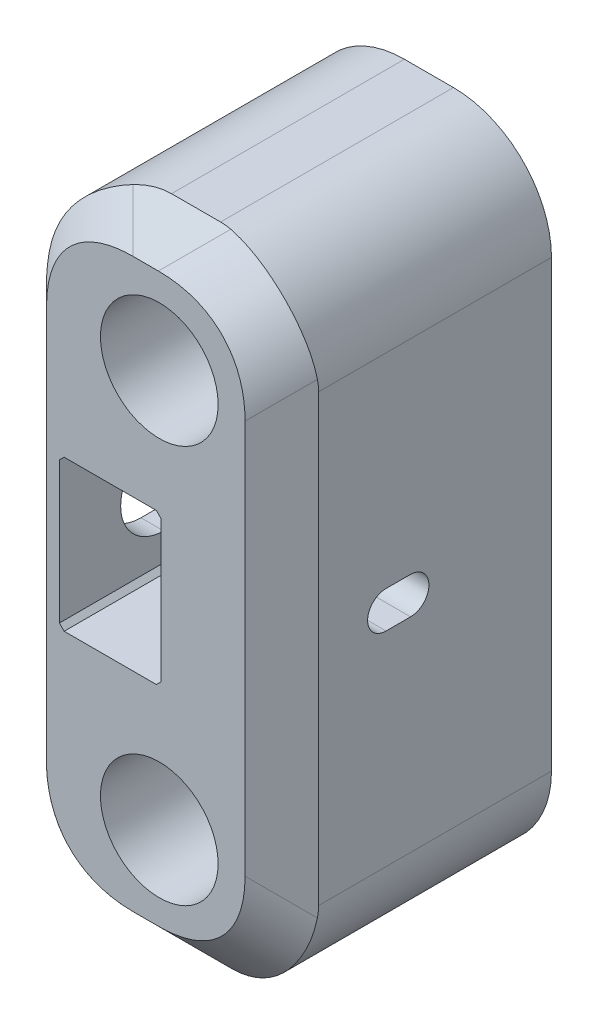
SolidWorks part; units mm, degrees
material "ABS"
ref_plane "Płaszczyzna przednia" through (0, 0, 0) normal (0, 0, 1) x (1, 0, 0)
ref_plane "Płaszczyzna górna" through (0, 0, 0) normal (0, 1, 0) x (1, 0, 0)
ref_plane "Płaszczyzna prawa" through (0, 0, 0) normal (1, 0, 0) x (0, 0, -1)
sketch "Szkic1" plane through (0, 0, 0) normal (0, 0, 1) x (1, 0, 0)
  line L0 (-32.7422, 138.1139) -> (-31.6012, 138.1139) construction
  line L1 (-31.3012, 137.8139) -> (-31.6012, 138.1139) construction
  line L2 (-31.3012, 137.8139) -> (-31.3012, 126.4139) construction
  line L3 (-31.6012, 126.1139) -> (-31.3012, 126.4139) construction
  line L4 (-31.6012, 126.1139) -> (-32.7422, 126.1139) construction
  line L5 (-33.0512, 126.6139) -> (-33.0512, 127.1139) construction
  line L6 (-33.0512, 127.1139) -> (-33.5512, 127.1139) construction
  line L7 (-33.5512, 127.1139) -> (-33.5512, 126.6139) construction
  line L8 (-39.3012, 126.4139) -> (-39.0012, 126.1139) construction
  line L9 (-33.8602, 126.1139) -> (-39.0012, 126.1139) construction
  line L10 (-39.3012, 126.4139) -> (-39.3012, 137.8139) construction
  line L11 (-39.0012, 138.1139) -> (-39.3012, 137.8139) construction
  line L12 (-33.5512, 137.6139) -> (-33.5512, 137.1139) construction
  line L13 (-33.5512, 137.1139) -> (-33.0512, 137.1139) construction
  line L14 (-33.0512, 137.1139) -> (-33.0512, 137.6139) construction
  line L15 (-39.0012, 138.1139) -> (-33.8602, 138.1139) construction
  line L16 (-21.3012, -182.8861) -> (-21.3012, 217.1139) construction
  line L17 (-41.3012, -182.8861) -> (-41.3012, 217.1139) construction
  line L18 (-28.2012, -182.8861) -> (-28.2012, 217.1139) construction
  line L19 (-34.4012, -182.8861) -> (-34.4012, 217.1139) construction
  line L20 (-33.8602, 138.1139) -> (-32.7422, 138.1139) construction
  line L21 (-33.8602, 126.1139) -> (-32.7422, 126.1139) construction
  line L22 (-33.8602, 125.9639) -> (-39.0633, 125.9639)
  line L23 (-39.4512, 126.3517) -> (-39.0633, 125.9639)
  line L24 (-39.4512, 126.3517) -> (-39.4512, 137.876)
  line L25 (-39.0633, 138.2639) -> (-39.4512, 137.876)
  line L26 (-39.0633, 138.2639) -> (-33.8602, 138.2639)
  line L27 (-33.5602, 126.1139) -> (-33.5602, 125.9639) construction
  line L28 (-32.7422, 138.2639) -> (-31.5391, 138.2639)
  line L29 (-31.1512, 137.876) -> (-31.5391, 138.2639)
  line L30 (-31.1512, 137.876) -> (-31.1512, 126.3517)
  line L31 (-31.5391, 125.9639) -> (-31.1512, 126.3517)
  line L32 (-31.5391, 125.9639) -> (-32.7422, 125.9639)
  line L33 (-33.5602, 125.9639) -> (-33.8602, 125.9639)
  line L36 (-33.417, 126.3455) -> (-33.1854, 126.3455) construction
  line L37 (-33.0422, 126.1139) -> (-33.0422, 125.9639) construction
  line L38 (-33.0422, 125.9639) -> (-32.7422, 125.9639)
  line L39 (-33.8602, 138.2639) -> (-33.5602, 138.2639)
  line L40 (-33.5602, 138.2639) -> (-33.5602, 138.1139) construction
  line L41 (-32.7422, 138.2639) -> (-33.0422, 138.2639)
  line L42 (-33.0422, 138.2639) -> (-33.0422, 138.1139) construction
  line L43 (-33.417, 137.8822) -> (-33.1854, 137.8822) construction
  line L44 (-41.3012, 132.1139) -> (-21.3012, 132.1139) construction
  line L45 (-41.3012, 105.9639) -> (-41.3012, 158.2639)
  line L46 (-41.3012, 158.2639) -> (-21.3012, 158.2639)
  line L47 (-21.3012, 158.2639) -> (-21.3012, 105.9639)
  line L48 (-41.3012, 105.9639) -> (-21.3012, 105.9639)
  line L49 (-31.3012, 158.2639) -> (-31.3012, 138.2639) construction
  line L50 (-33.5602, 138.2639) -> (-33.0422, 138.2639)
  line L51 (-33.5602, 125.9639) -> (-33.0422, 125.9639)
  arc A0 (-32.7422, 126.1139) -> (-33.0512, 126.6139) centre (-33.3012, 126.1139) ccw construction
  arc A1 (-33.5512, 126.6139) -> (-33.8602, 126.1139) centre (-33.3012, 126.1139) ccw construction
  arc A2 (-33.0512, 137.6139) -> (-32.7422, 138.1139) centre (-33.3012, 138.1139) ccw construction
  arc A3 (-33.8602, 138.1139) -> (-33.5512, 137.6139) centre (-33.3012, 138.1139) ccw construction
  arc A4 (-33.417, 126.3455) -> (-33.5602, 126.1139) centre (-33.3012, 126.1139) ccw construction
  arc A5 (-33.0422, 126.1139) -> (-33.1854, 126.3455) centre (-33.3012, 126.1139) ccw construction
  arc A6 (-33.5602, 138.1139) -> (-33.417, 137.8822) centre (-33.3012, 138.1139) ccw construction
  arc A7 (-33.1854, 137.8822) -> (-33.0422, 138.1139) centre (-33.3012, 138.1139) ccw construction
  circle A8 centre (-31.3012, 148.2639) radius 2.8
  circle A9 centre (-31.3012, 115.9639) radius 2.8
  point P70 (-39.4512, 132.1139)
  dimension "D2" = 20
extrude "Dodanie-wyciągnięcie1" add sketch "Szkic1" along normal blind 22
sketch "Szkic2" plane through (0, 0, 22) normal (0, 0, 1) x (1, 0, 0)
  circle A0 centre (-31.3012, 148.2639) radius 4.8
  circle A1 centre (-31.3012, 115.8139) radius 4.8
extrude "Wytnij-wyciągnięcie1" cut sketch "Szkic2" against normal blind 7
fillet "Zaokrąglenie1" radius 8 4 edges at (-21.3012, 105.9639, 11) (-41.3012, 105.9639, 11) (-41.3012, 158.2639, 11) (-21.3012, 158.2639, 11)
sketch "Szkic4" plane through (-39.4512, 0, 0) normal (1, 0, 0) x (0, 0, -1)
  line L0 (-22, 132.1139) -> (0, 132.1139) construction
  line L1 (-22, 137.876) -> (-22, 126.3517) construction
  line L2 (0, 137.876) -> (0, 126.3517) construction
  line L3 (-13.5, 132.1139) -> (-11.5, 132.1139) construction
  line L4 (-13.5, 133.6139) -> (-11.5, 133.6139)
  line L5 (-13.5, 130.6139) -> (-11.5, 130.6139)
  arc A0 (-13.5, 133.6139) -> (-13.5, 130.6139) centre (-13.5, 132.1139) ccw
  arc A1 (-11.5, 130.6139) -> (-11.5, 133.6139) centre (-11.5, 132.1139) ccw
  point P8 (-12.5, 132.1139)
  dimension "D1" = 11.5
  dimension "D2" = 13.5
  dimension "D3" = 3
extrude "Wytnij-wyciągnięcie2" cut sketch "Szkic4" against normal through all both and the other way through all
sketch "Szkic6" plane through (-41.3012, 0, 0) normal (-1, 0, 0) x (0, 0, 1)
  line L6 (11.5, 128.6139) -> (13.5, 128.6139)
  line L7 (13.5, 135.6139) -> (11.5, 135.6139)
  line L8 (11.5, 128.6139) -> (13.5, 128.6139)
  line L9 (13.5, 135.6139) -> (11.5, 135.6139)
  arc A8 (13.5, 128.6139) -> (13.5, 135.6139) centre (13.5, 132.1139) ccw
  arc A9 (11.5, 135.6139) -> (11.5, 128.6139) centre (11.5, 132.1139) ccw
  arc A10 (13.5, 128.6139) -> (13.5, 135.6139) centre (13.5, 132.1139) ccw
  arc A11 (11.5, 135.6139) -> (11.5, 128.6139) centre (11.5, 132.1139) ccw
  dimension "D1" = 2
extrude "Wytnij-wyciągnięcie3" cut sketch "Szkic6" against normal up to next
sketch "Szkic7" plane through (0, 0, 0) normal (0, 0, -1) x (-1, 0, 0)
  line L0 (31.5391, 125.9639) -> (31.1512, 126.3517) construction
  line L1 (39.0633, 125.9639) -> (31.5391, 125.9639) construction
  line L2 (39.4512, 126.3517) -> (39.0633, 125.9639) construction
  line L3 (39.4512, 137.876) -> (39.4512, 126.3517) construction
  line L4 (39.0633, 138.2639) -> (39.4512, 137.876) construction
  line L5 (31.1512, 137.876) -> (31.5391, 138.2639) construction
  line L6 (31.1512, 126.3517) -> (31.1512, 137.876) construction
  line L7 (31.5391, 138.2639) -> (39.0633, 138.2639) construction
  line L8 (31.5391, 125.9639) -> (31.1512, 126.3517)
  line L9 (39.0633, 125.9639) -> (31.5391, 125.9639)
  line L10 (39.4512, 126.3517) -> (39.0633, 125.9639)
  line L11 (39.4512, 137.876) -> (39.4512, 126.3517)
  line L12 (39.0633, 138.2639) -> (39.4512, 137.876)
  line L13 (31.1512, 137.876) -> (31.5391, 138.2639)
  line L14 (31.1512, 126.3517) -> (31.1512, 137.876)
  line L15 (31.5391, 138.2639) -> (39.0633, 138.2639)
  circle A0 centre (31.3012, 115.9639) radius 2.8 construction
  circle A1 centre (31.3012, 148.2639) radius 2.8 construction
  circle A2 centre (31.3012, 115.9639) radius 2.8
  circle A3 centre (31.3012, 148.2639) radius 2.8
extrude "Dodanie-wyciągnięcie2" add sketch "Szkic7" against normal blind 0.2
chamfer "Sfazowanie1" distance 3 angle 45 1 edges at (-21.3012, 132.1139, 22) tangent propagation no
chamfer "Sfazowanie2" distance 3 angle 45 2 edges at (-31.3012, 105.9639, 22) (-31.3012, 158.2639, 22) tangent propagation no
fillet "Zaokrąglenie2" radius 10 2 edges at (-23.9728, 108.6354, 21.6716) (-23.9728, 155.5923, 21.6716)
chamfer "Sfazowanie3" distance 0.8 angle 45 3 edges at (-40.8497, 152.9134, 22) (-40.8497, 111.3143, 22) (-41.3012, 132.1139, 22)
fillet "Zaokrąglenie3" radius 10 2 edges
